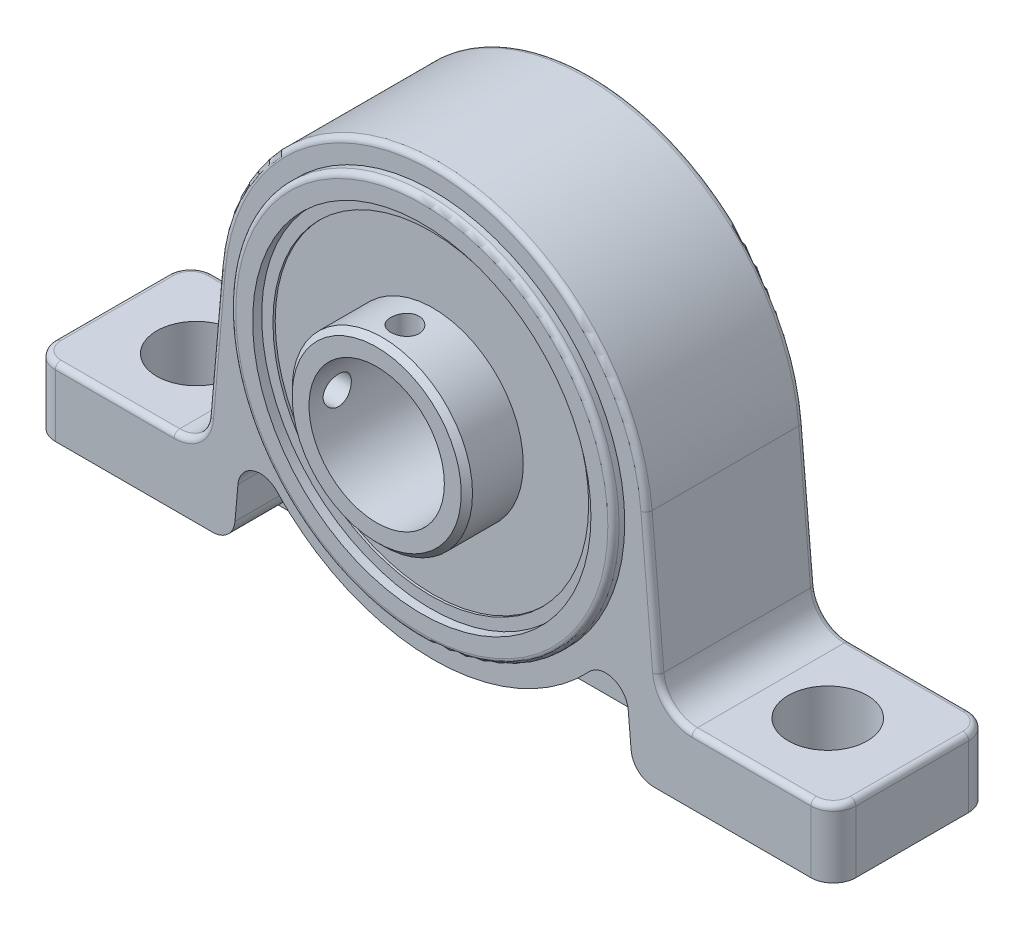
SolidWorks part; units mm, degrees
ref_plane "Front Plane" through (0, 0, 0) normal (0, 0, 1) x (1, 0, 0)
ref_plane "Top Plane" through (0, 0, 0) normal (0, 1, 0) x (1, 0, 0)
ref_plane "Right Plane" through (0, 0, 0) normal (1, 0, 0) x (0, 0, -1)
sketch "Sketch1" plane through (0, 0, 0) normal (0, 0, 1) x (1, 0, 0)
  line L0 (0, 0) -> (-11670.9506, 0) construction
  line L1 (0, 0) -> (0, 11670.9506) construction
  line L2 (-35.5, 0) -> (-35.5, 6)
  line L3 (-35.5, 6) -> (-22.9589, 6)
  line L4 (-35.5, 0) -> (-19.5561, 0)
  line L5 (-17.5637, 1.8257) -> (-17.3033, 4.8016)
  line L6 (-19.9703, 8.7385) -> (-18.9277, 20.656)
  line L7 (35.5, -4.905) -> (-35.5, -4.905) construction
  line L8 (13, -4.905) -> (13, -1.8884) construction
  line L9 (-13, -4.905) -> (-13, -1.8884) construction
  line L10 (0, 0) -> (11670.9506, 0) construction
  line L11 (19.9703, 8.7385) -> (18.9277, 20.656)
  line L12 (17.5637, 1.8257) -> (17.3033, 4.8016)
  line L13 (35.5, 0) -> (19.5561, 0)
  line L14 (35.5, 6) -> (22.9589, 6)
  line L15 (35.5, 0) -> (35.5, 6)
  circle A0 centre (0, 19) radius 6
  arc A1 (-13.8527, 5.9961) -> (13.8527, 5.9961) centre (0, 19) ccw
  circle A2 centre (0, 19) radius 17
  arc A3 (-19.9703, 8.7385) -> (-22.9589, 6) centre (-22.9589, 9) cw
  arc A4 (-17.5637, 1.8257) -> (-19.5561, 0) centre (-19.5561, 2) cw
  arc A5 (-13.8527, 5.9961) -> (-17.3033, 4.8016) centre (-15.3109, 4.6273) ccw
  circle A6 centre (0, 19) radius 19 construction
  circle A7 centre (0, 19) radius 8
  circle A8 centre (0, 19) radius 15
  circle A9 centre (0, 19) radius 14
  arc A10 (13.8527, 5.9961) -> (17.3033, 4.8016) centre (15.3109, 4.6273) cw
  arc A11 (17.5637, 1.8257) -> (19.5561, 0) centre (19.5561, 2) ccw
  arc A12 (19.9703, 8.7385) -> (22.9589, 6) centre (22.9589, 9) ccw
  arc A13 (18.9277, 20.656) -> (-18.9277, 20.656) centre (0, 19) ccw
  point P18 (0, -4.905)
  point P33 (-17.7234, 0)
  point P34 (14.3446, 20.3856)
  point P57 (17.7234, 0)
  dimension "D1" = 12
  dimension "D2" = 19
  dimension "D3" = 38
  dimension "D10" = 3
  dimension "D11" = 2
  dimension "D12" = 2
  dimension "D4" = 71
  dimension "D6" = 6
  dimension "D7" = 3
  dimension "D9" = 85
  dimension "D8" = 2
  dimension "D13" = 2
  dimension "D14" = 2
  dimension "D15" = 1
extrude "B" add sketch "Sketch1" along normal blind 14 contours L11 A13 L6 A3 L3 L2 L4 A4 L5 A5 A1 A10 L12 A11 L13 L15 L14 A12 A2 region at (-34.6947, 3, 0)
extrude "B1S" add sketch "Sketch1<3>" along normal blind 12 from offset 3 contours A2 A8 region at (-16.5192, 19, 0)
sketch "Sketch1<3>" plane through (0, 0, 0) normal (0, 0, 1) x (1, 0, 0) same geometry as "Sketch1"
extrude "Boss-Extrude3" add sketch "Sketch1<4>" along normal blind 11 from offset 3.2 contours A8 A9 region at (-14.5757, 19, 0)
sketch "Sketch1<4>" plane through (0, 0, 0) normal (0, 0, 1) x (1, 0, 0) same geometry as "Sketch1"
extrude "Boss-Extrude4" add sketch "Sketch1<6>" along normal blind 10.5 from offset 3.5 contours A9 A7 region at (-13.604, 19, 0)
sketch "Sketch1<6>" plane through (0, 0, 0) normal (0, 0, 1) x (1, 0, 0) same geometry as "Sketch1"
extrude "A" add sketch "Sketch1<7>" along normal blind 16 from offset 3 contours A7 A0 region at (-7.7737, 19, 0)
sketch "Sketch1<7>" plane through (0, 0, 0) normal (0, 0, 1) x (1, 0, 0) same geometry as "Sketch1"
ref_plane "Plane1" through (0, 0, 7) normal (0, 0, 1) x (1, 0, 0)
sketch "Sketch2" plane through (0, 0, 7) normal (0, 0, 1) x (1, 0, 0)
  line L0 (19.5561, 0) -> (-19.5561, 0)
  line L1 (-19.5561, 0) -> (-19.5561, 5.5)
  line L2 (-19.5561, 5.5) -> (19.5561, 5.5)
  line L3 (19.5561, 5.5) -> (19.5561, 0)
  dimension "D1" = 39.1121
  dimension "D2" = 5.5
extrude "Boss-Extrude6" add sketch "Sketch2" along normal mid plane 4
sketch "Sketch3" plane through (0, 0, 0) normal (1, 0, 0) x (0, 0, -1)
  line L0 (-18, 19) -> (49982, 19) construction
  line L1 (-19, 27) -> (-19, 11) construction
  line L2 (-16.5, 22) -> (-16.5, -49978) construction
  line L3 (-14, 27) -> (-19, 27) construction
  circle A0 centre (-16.5, 19) radius 1.25
  point P4 (-19, 19)
  point P9 (-16.5, 27)
  dimension "D1" = 2.5
extrude "Cut-Extrude1" cut sketch "Sketch3" against normal up to next
pattern_circular "CirPattern1" count 2 over 90 about axis through (0, 19, 19) along (0, 0, -1) of "Cut-Extrude1"
fillet "Fillet1" radius 2 4 edges at (-35.5, 3, 0) (-35.5, 3, 14) (35.5, 3, 0) (35.5, 3, 14)
fillet "Fillet2" radius 0.5 21 edges at (19.449, 14.6972, 14) (20.9322, 6.7882, 14) (28.2295, 6, 14) (34.9142, 6, 13.4142) (35.5, 6, 7) (34.9142, 6, 0.5858) (28.2295, 6, 0) (20.9322, 6.7882, 0) (19.449, 14.6972, 0) (0, 38, 0) (-19.449, 14.6972, 0) (-20.9322, 6.7882, 0) (-28.2295, 6, 0) (-34.9142, 6, 0.5858) (-35.5, 6, 7) (-34.9142, 6, 13.4142) (-28.2295, 6, 14) (-20.9322, 6.7882, 14) (-19.449, 14.6972, 14) (0, 38, 14) (17, 19, 15)
fillet "Fillet3" radius 1 1 edges at (17, 19, 0)
chamfer "Chamfer1" distance 0.5 angle 45 1 edges at (8, 19, 19)
sketch "Sketch4" plane through (0, 6, 0) normal (0, 1, 0) x (1, 0, 0)
  line L0 (35.5, -7) -> (-35.5, -7) construction
  line L1 (35.5, -2) -> (35.5, -12) construction
  line L2 (-35.5, -12) -> (-35.5, -2) construction
  line L3 (-35.5, -7) -> (0, 0) construction
  line L4 (0, 0) -> (0, -18.5) construction
  line L5 (8, -18.5) -> (-8, -18.5) construction
  circle A0 centre (28, -7) radius 3.5
  circle A1 centre (-28, -7) radius 3.5
  dimension "D1" = 7
  dimension "D2" = 56
extrude "Cut-Extrude2" cut sketch "Sketch4" against normal through all
